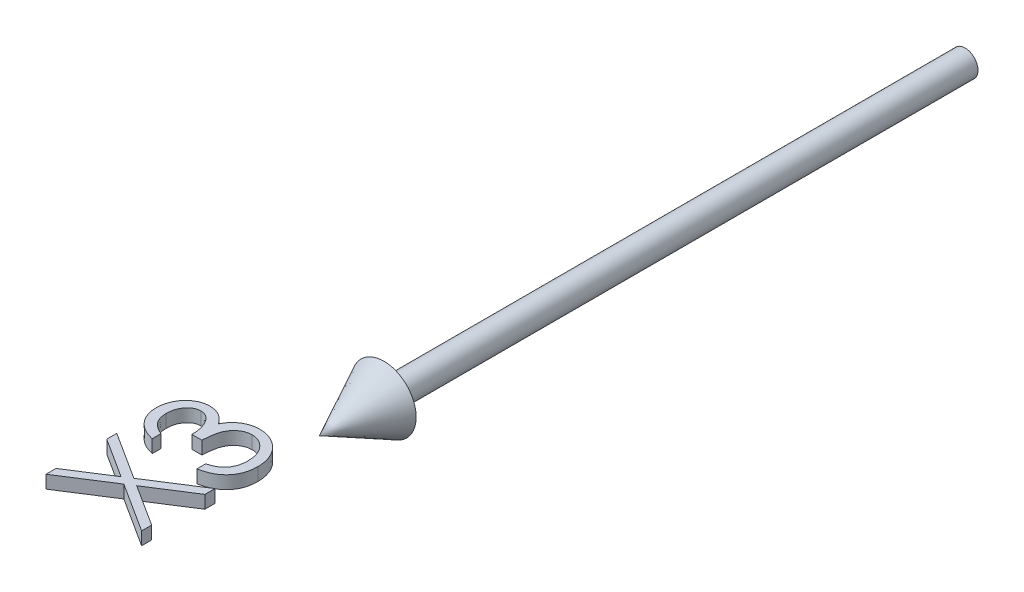
SolidWorks part; units mm, degrees
ref_plane "Front Plane" through (0, 0, 0) normal (0, 0, 1) x (1, 0, 0)
ref_plane "Top Plane" through (0, 0, 0) normal (0, 1, 0) x (1, 0, 0)
ref_plane "Right Plane" through (0, 0, 0) normal (1, 0, 0) x (0, 0, -1)
sketch "Sketch2" plane through (0, 0, 0) normal (0, 1, 0) x (1, 0, 0)
  line L0 (0, 41.95) -> (0, -114.4521) construction
  line L1 (-36.8894, 0) -> (41.4965, 0) construction
  line L2 (0, -100) -> (5, -90)
  line L3 (5, -90) -> (2, -90)
  line L4 (2, -90) -> (2, 0)
  line L5 (2, 0) -> (0, 0)
  line L6 (0, 0) -> (0, -100)
  dimension "D1" = 100
  dimension "D2" = 2
  dimension "D3" = 10
  dimension "D4" = 5
revolve "Revolve1" add sketch "Sketch2" angle 360 about L0
sketch "Sketch3" plane through (0, 0, 0) normal (0, 1, 0) x (1, 0, 0)
  line L0 (0, -103.9528) -> (0, -147.2622) construction
  line L1 (-18.6107, -118.3811) -> (18.3141, -118.3811) construction
  text T0 "X3" font "Century Gothic" height 15
extrude "Boss-Extrude1" add sketch "Sketch3" against normal blind 1 and the other way blind 1 separate body
equation "\"frame_arrow_length\"=100"
equation "\"D1@Sketch2\"=\"frame_arrow_length\""
equation "\"frame_arrow_odA\"=4"
equation "\"D2@Sketch2\"=\"frame_arrow_odA\"/2"
equation "\"frame_arrow_head_od\"=5"
equation "\"D4@Sketch2\"=\"frame_arrow_head_od\""
equation "\"frame_arrow_head_length\"=10"
equation "\"D3@Sketch2\"=\"frame_arrow_head_length\""
equation "\"tvarobot_theta1\"=30"
equation "\"link0_ringA_odA\"= 40"
equation "\"link0_ringA_odB\"= 25"
equation "\"link0_ringA_id\"= 20"
equation "\"link0_ringA_thickness\"= (\"link0_ringA_odB\" - \"link0_ringA_id\")/2"
equation "\"link0_ringA_height\"= 3"
equation "\"link0_ringA_heightA\"= 1.5"
equation "\"link0_ringA_heightB\"=\"link0_ringA_height\"-\"link0_ringA_heightA\""
equation "\"link0_ringB_odA\"= 40"
equation "\"link0_ringB_odB\"= 29"
equation "\"link0_ringB_id\"= \"link0_shaftA_bearing_id\"+1"
equation "\"link0_ringB_thickness\"= (\"link0_ringB_odB\" - \"link0_ringB_id\")/2"
equation "\"link0_ringB_height\"= 3"
equation "\"link0_ringB_heightA\"= 1.5"
equation "\"link0_ringB_heightB\"=\"link0_ringB_height\"-\"link0_ringB_heightA\""
equation "\"link0_shaftA_bearing_od\"=27"
equation "\"link0_shaftA_bearing_id\"=20"
equation "\"link0_shaftA_thrust_bearing_od\"=35"
equation "\"link0_shaftA_thrust_bearing_id\"=20.04"
equation "\"link0_shaftA_retaining_ring_id\"=18.5"
equation "\"link0_shaftA_retaining_ring_groove_width\"=1.5"
equation "\"link0_shaftA_spline_length\"=8.0"
equation "\"link0_shaftA_spline_depth\"=1.0"
equation "\"link0_shaftA_spline_width\"=4.0"
equation "\"link0_shaftA_odA\"=\"link0_shaftA_bearing_id\""
equation "\"link0_shaftA_odB\"=35"
equation "\"link0_shaftA_odC\"=\"link0_shaftA_bearing_id\""
equation "\"link0_shaftA_odD\"=\"link0_shaftA_odC\"-2*\"link0_shaftA_spline_depth\""
equation "\"link0_shaftA_odE\"=\"link0_shaftA_bearing_id\""
equation "\"link0_shaftA_odF\"=\"link0_shaftA_odE\"-2*\"link0_shaftA_spline_depth\""
equation "\"link0_shaftA_idA\"=10"
equation "\"link0_shaftA_idB\"=6"
equation "\"link0_shaftA_length\"=39.5"
equation "\"link0_shaftA_lengthA\"=8.0"
equation "\"link0_shaftA_lengthB\"=12.0"
equation "\"link0_shaftA_lengthC\"=35.0"
equation "\"link0_shaftA_lengthD\"=39.0"
equation "\"link0_shaftA_lengthE\"=\"link0_shaftA_length\"-\"link0_shaftA_lengthD\""
equation "\"link0_shaftA_offsetX\"=11"
equation "\"link0_shaftA_offsetY\"=0"
equation "\"link0_shaftA_bolt_pattern_dia\"=14"
equation "\"link0_motor_center_dist\"=26"
equation "\"link0_46t_pulley_spline_length\"=8"
equation "\"link0_46t_pulley_spline_depth\"=\"link0_shaftA_spline_depth\"*1.025"
equation "\"link0_46t_pulley_spline_width\"=\"link0_shaftA_spline_width\"*1.05"
equation "\"link0_46t_pulley_idA\"=\"link0_shaftA_bearing_id\"*1.025"
equation "\"link0_46t_pulley_idB\"=\"link0_46t_pulley_idA\"-2*\"link0_46t_pulley_spline_depth\""
equation "\"link0_shaftB_spline_length\"=10"
equation "\"link0_shaftB_spline_depth\"=1.0"
equation "\"link0_shaftB_spline_width\"=1.25"
equation "\"link0_shaftB_length\"=7"
equation "\"link0_shaftB_lengthA\"=1.5"
equation "\"link0_shaftB_lengthB\"=2.75"
equation "\"link0_shaftB_odA\"=32"
equation "\"link0_shaftB_odB\"=22"
equation "\"link0_shaftB_odC\"=20"
equation "\"link0_shaftB_idA\"=10"
equation "\"link0_shaftB_bolt_diameter\"=19"
equation "\"link0_shaftB_bearing_od\"=27"
equation "\"link0_shaftB_bearing_id\"=20"
equation "\"link0_motor_length\"=46.5"
equation "\"link0_motor_width\"=28.5"
equation "\"link0_motor_height\"=34"
equation "\"link0_motor_offset\"=8"
equation "\"link0_shellA_thickness\"=2.5"
equation "\"link0_shellB_thickness\"=\"link0_shellA_thickness\""
equation "\"link0_plateA_shellA_height\"=48"
equation "\"link0_shellA_width\" =\"link0_plateA_width\""
equation "\"link0_shellA_height\" = \"link0_plateA_shellA_height\"-\"link0_plateA_height\""
equation "\"link0_shellA_length\" = \"link0_plateA_lengthB\" "
equation "\"link0_shellB_length\"=\"link0_shellA_length\""
equation "\"link0_shellA_radius\" = 0.375*25.4"
equation "\"link0_shellA_radiusA\"= \"link0_plateA_radiusA\""
equation "\"link0_shellA_radiusB\"= \"link0_plateA_radiusB\""
equation "\"link0_shellA_radiusC\"= 3"
equation "\"link0_postA_height\"=7"
equation "\"link0_postA_width\"=16"
equation "\"link0_postA_length\"=20"
equation "\"link0_postA_posX\"=22"
equation "\"link0_postA_posY\"=17.5"
equation "\"link0_postA_pocket_width\"=6.0"
equation "\"link0_postA_pocket_length\"=2.5"
equation "\"link0_postA_pocket_depth\"=9"
equation "\"link0_postA_pocket_posZ\"=10"
equation "\"link0_postB_height\"=7"
equation "\"link0_postB_width\"=16"
equation "\"link0_postB_length\"=20"
equation "\"link0_postB_posX\"=22"
equation "\"link0_postB_posY\"=17.5"
equation "\"link0_postB_id\"=3.0"
equation "\"link0_postB_pocket_width\"=6.0"
equation "\"link0_postB_pocket_length\"=2.5"
equation "\"link0_postB_pocket_depth\"=9"
equation "\"link0_postB_pocket_posZ\"=10"
equation "\"link0_postC_height\"=7"
equation "\"link0_postC_width\"=16"
equation "\"link0_postC_length\"=20"
equation "\"link0_postC_posX\"=22"
equation "\"link0_postC_posY\"=17.5"
equation "\"link0_postC_id\"=3.0"
equation "\"link0_postC_pocket_width\"=6.0"
equation "\"link0_postC_pocket_length\"=2.5"
equation "\"link0_postC_pocket_depth\"=9"
equation "\"link0_postC_pocket_posZ\"=10"
equation "\"link0_postD_height\"=7"
equation "\"link0_postD_width\"=16"
equation "\"link0_postD_length\"=20"
equation "\"link0_postD_posX\"=22"
equation "\"link0_postD_posY\"=17.5"
equation "\"link0_postD_id\"=3.0"
equation "\"link0_postD_pocket_width\"=6.0"
equation "\"link0_postD_pocket_length\"=3.0"
equation "\"link0_postD_pocket_depth\"=9"
equation "\"link0_postD_pocket_posZ\"=10"
equation "\"link0_postE_height\"=5"
equation "\"link0_postE_width\"=16"
equation "\"link0_postE_length\"=\"link0_plateE_lengthA\"-\"link0_lip_height\""
equation "\"link0_postE_posZ\"=22"
equation "\"link0_postE_posX\"=17.5"
equation "\"link0_postE_posY\"=22"
equation "\"link0_postE_id\"=3.0"
equation "\"link0_postE_cbore_id\"=6.5"
equation "\"link0_postE_hole_id\"=3"
equation "\"link0_postF_posZ\"=22"
equation "\"link0_postF_posX\"=17.5"
equation "\"link0_postF_posY\"=\"link0_plateB_lengthA\"+4"
equation "\"link0_postF_id\"=3.0"
equation "\"link0_postF_cbore_id\"=6.5"
equation "\"link0_postF_hole_id\"=3"
equation "\"link0_postG_posZ\"=22"
equation "\"link0_postG_posX\"=17.5"
equation "\"link0_postG_posY\"=\"link0_plateB_lengthA\"+12"
equation "\"link0_postG_id\"=3.0"
equation "\"link0_postG_cbore_id\"=6.5"
equation "\"link0_postG_hole_id\"=3"
equation "\"link0_postHIJ_posY\"=6"
equation "\"link0_postH_posX\"=28"
equation "\"link0_postH_posY\"=20"
equation "\"link0_postH_posZ\"=20"
equation "\"link0_postH_length\"=10"
equation "\"link0_postI_posX\"=28"
equation "\"link0_postI_posY\"=20"
equation "\"link0_postI_posZ\"=135"
equation "\"link0_postI_length\"=10"
equation "\"link0_postJ_posX\"=28"
equation "\"link0_postJ_posY\"=20"
equation "\"link0_postJ_posZ\"=175"
equation "\"link0_postJ_length\"=10"
equation "\"link0_postK_posX\"=28"
equation "\"link0_postK_posY\"=20"
equation "\"link0_postK_posZ\"=175"
equation "\"link0_postK_length\"=10"
equation "\"link0_postL_posX\"=28"
equation "\"link0_postL_posY\"=20"
equation "\"link0_postL_posZ\"=135"
equation "\"link0_postL_length\"=10"
equation "\"link0_postM_posX\"=28"
equation "\"link0_postM_posY\"=20"
equation "\"link0_postM_posZ\"=35"
equation "\"link0_postM_length\"=10"
equation "\"link0_plateA_lengthA\"=30"
equation "\"link0_plateA_lengthB\"=150"
equation "\"link0_plateA_lengthC\"=30"
equation "\"link0_plateA_length\"=\"link0_plateA_lengthA\"+\"link0_plateA_lengthB\"+\"link0_plateA_lengthC\""
equation "\"link0_plateA_width\"=  68"
equation "\"link0_plateA_height\"= \"link0_plateA_radiusA\""
equation "\"link0_plateA_thickness\"=\"link0_shellA_thickness\""
equation "\"link0_plateA_radius\"= 9.5"
equation "\"link0_plateA_radiusA\"= 18"
equation "\"link0_plateA_radiusB\"= 18"
equation "\"link0_plateA_radiusC\"= 3"
equation "\"link0_plateB_length\"= 40"
equation "\"link0_plateB_width\"= \"link0_plateA_width\"*1.005"
equation "\"link0_plateB_height\"= \"link0_plateA_shellA_height\"*1.005"
equation "\"link0_plateB_lengthA\"=\"link0_lip_height\"+\"link0_plateD_thickness\"+\"link0_motor_mount_thickness\""
equation "\"link0_plateB_lengthB\"=\"link0_plateB_height\"-\"link0_plateB_lengthA\""
equation "\"link0_plateB_radiusA\"= \"link0_plateA_radiusA\""
equation "\"link0_plateB_radiusB\"= \"link0_plateA_radiusB\""
equation "\"link0_plateB_radiusC\"= 3"
equation "\"link0_plateB_idA\"=\"link0_shaftA_odC\"+1"
equation "\"link0_plateB_idB\"=\"link0_shaftA_bearing_od\"-2"
equation "\"link0_plateB_idC\"=\"link0_shaftA_bearing_od\"*1.005"
equation "\"link0_plateB_idD\"=\"link0_shaftA_thrust_bearing_od\"+1 "
equation "\"link0_plateB_depthA\"=1.0"
equation "\"link0_plateB_depthB\"=2.0"
equation "\"link0_plateB_depthC\"=8"
equation "\"link0_plateB_depthD\"=\"link0_plateB_length\"-\"link0_lip_height\"-\"link0_plateD_thickness\" "
equation "\"link0_plateC_length\"=\"link0_plateB_length\""
equation "\"link0_plateC_width\"= \"link0_plateB_width\""
equation "\"link0_plateC_height\"= .1*25.4"
equation "\"link0_plateA_hole_od\" = 0.1*25.4"
equation "\"link0_plateA_hole_delx\" = 0.5*25.4"
equation "\"link0_plateA_hole_delz\" = 0.75*25.4"
equation "\"link0_plateA_hole_offx\" = 0.0*25.4"
equation "\"link0_plateA_hole_offz\" = \"link0_plateA_length\"/2"
equation "\"link0_plateB_hole_od\" = 0.1*25.4"
equation "\"link0_plateB_hole_delx\"= 0.75*25.4"
equation "\"link0_plateB_hole_delz\"= 0.75*25.4"
equation "\"link0_plateB_hole_offx\"= 0.0*25.4"
equation "\"link0_plateB_hole_offz\"= 0.0*25.4"
equation "\"link0_plateC_hole_od\"= 0.1*25.4"
equation "\"link0_plateC_hole_delx\"= 0.75*25.4"
equation "\"link0_plateC_hole_delz\"= 0.75*25.4"
equation "\"link0_plateC_hole_offx\"= 0.0*25.4"
equation "\"link0_plateC_hole_offz\"= 0.0*25.4"
equation "\"link0_plateD_height\"=\"link0_plateB_height\"-2*\"link0_shellA_thickness\""
equation "\"link0_plateD_width\"=\"link0_plateB_width\"-2*\"link0_shellA_thickness\""
equation "\"link0_plateD_thickness\"=10"
equation "\"link0_plateD_radiusA\"=\"link0_plateB_radiusA\"-\"link0_shellA_thickness\""
equation "\"link0_plateD_odA\"= .375*25.4"
equation "\"link0_plateD_odB\"= .375*25.4"
equation "\"link0_plateD_bearing_id\"=20"
equation "\"link0_plateD_bearing_od\"=27"
equation "\"link0_plateE_radiusA\"=\"link0_plateA_radiusA\""
equation "\"link0_plateE_radiusB\"=\"link0_plateA_radiusB\""
equation "\"link0_plateE_radiusC\"=8.0"
equation "\"link0_plateE_length\"=30"
equation "\"link0_plateE_lengthA\"=16"
equation "\"link0_plateE_height\"=\"link0_plateB_height\""
equation "\"link0_plateE_width\"=\"link0_plateB_width\""
equation "\"link0_plateE_odA\"=\"gantry_coupler_id\"*0.99"
equation "\"link0_plateE_idA\"=\"link0_plateE_odA\"-20.0"
equation "\"link0_plateE_spline_depth\"=\"link0_poleA_spline_depth\"*1.05"
equation "\"link0_plateE_spline_width\"=\"link0_poleA_spline_width\"*1.075"
equation "\"link0_plateE_spline_length\"=\"link0_poleA_spline_length\""
equation "\"link0_plateE_coupler_length\"=46"
equation "\"link0_lip_height\"=5.0"
equation "\"link0_lip_thickness\"=2.0"
equation "\"link0_motor_mount_thickness\"=8.0"
equation "\"link0_motor_mount_idA\"=22"
equation "\"link0_motor_mount_idB\"=\"link0_shaftB_bearing_od\"*1.005"
equation "\"link0_motor_mount_idC\"=\"link0_shaftB_bearing_od\"-2"
equation "\"link0_motor_mount_depthA\"=5.5"
equation "\"link0_motor_mount_height\"=\"link0_plateD_height\""
equation "\"link0_motor_mount_width\"=\"link0_plateD_width\""
equation "\"link0_motor_mountL_height\"=36"
equation "\"link0_motor_mountL_heightA\"=12"
equation "\"link0_motor_mountL_length\"=50"
equation "\"link0_motor_mountL_lengthA\"=36"
equation "\"gantry_coupler_od\"=25.4*2.0"
equation "\"gantry_coupler_id\"=1.645*25.4"
equation "\"gantry_coupler_offsetX\"=\"link0_plateE_width\"/2"
equation "\"link0_poleA_odA\"=20"
equation "\"link0_poleA_odB\"=36"
equation "\"link0_poleA_idA\"=\"link0_poleA_odA\"-2*\"link0_poleA_thickness\""
equation "\"link0_poleA_idB\"=(\"link0_plateE_idA\"/2+1.5*\"link0_lip_thickness\")*1.04"
equation "\"link0_poleA_thickness\"=3.5"
equation "\"link0_poleA_length\"=100"
equation "\"link0_poleA_lengthA\"=18.5"
equation "\"link0_poleA_lengthB\"=80"
equation "\"link0_poleA_gasket_thickness\"=1.5"
equation "\"link0_poleA_spline_depth\"=1.0"
equation "\"link0_poleA_spline_width\"=4.0"
equation "\"link0_poleA_spline_length\"=10.0"
equation "\"link1_plateB_length\"=30"
equation "\"link1_lip_height\"=\"link0_lip_height\""
equation "\"link0_tension_plateA_width\"=12"
equation "\"link0_tension_plateA_lengthA\"=10.5"
equation "\"link0_tension_plateB_width\"=\"link0_tension_plateA_width\""
equation "\"link0_tension_plateB_lengthA\"=\"link0_tension_plateA_lengthA\""
equation "\"link0_tension_wheelA_posZ\"=7"
equation "\"link0_tension_wheelA_posX\"=\"link0_plateD_height\"/2-\"link0_tension_plateA_lengthA\""
equation "\"link0_m2_clear_hole_id\"=2.35"
equation "\"link0_m2_insert_hole_id\"=2.5"
equation "\"link0_m2_tap_hole_id\"=1.75"
equation "\"link0_m2_nut_socket_width\"=4.25"
equation "\"link0_m2_nut_socket_depth\"=2.5"
equation "\"link0_m2_cbore_id\"=3.75"
equation "\"link0_m2_cbore_depth\"=7"
equation "\"link0_m2_5_clear_hole_id\"=2.75"
equation "\"link0_m2_5_insert_hole_id\"=2.75"
equation "\"link0_m2_5_tap_hole_id\"=2.25"
equation "\"link0_m2_5_nut_socket_width\"=5.25"
equation "\"link0_m2_5_nut_socket_depth\"=2.5"
equation "\"link0_m2_5_cbore_id\"=4.75"
equation "\"link0_m2_5_cbore_depth\"=2.5"
equation "\"link0_m2_5_insert_access_length\"=6.0"
equation "\"link0_m2_5_insert_access_width\"=3.0"
equation "\"link0_m3_clear_hole_id\"=3.25"
equation "\"link0_m3_insert_hole_id\"=3"
equation "\"link0_m3_tap_hole_id\"=2.75"
equation "\"link0_m3_nut_socket_width\"=5.75"
equation "\"link0_m3_nut_socket_depth\"=4.0"
equation "\"link0_m3_cbore_id\"=5.75"
equation "\"link0_m3_cbore_depth\"=3.5"
equation "\"link0_m3_insert_access_length\"=4.5"
equation "\"link0_m3_insert_access_width\"=3.5"
equation "\"link0_rpi_mount_height\"=6"
equation "\"link0_rpi_mount_width\"=49"
equation "\"link0_rpi_mount_length\"=58"
equation "\"link0_rpi_mount_post_od\"=6"
equation "\"link0_rpi_mount_posZ\"=72"
equation "\"link0_rpi_mount_posX\"=11.5"
equation "\"link0_mcu_mount_height\"=5"
equation "\"link0_mcu_mount_width\"=49"
equation "\"link0_mcu_mount_length\"=58"
equation "\"link0_mcu_mount_post_od\"=6"
equation "\"link0_mcu_mount_posZ\"=164"
equation "\"link0_mcu_mount_posX\"=4"
equation "\"link0_pwr_mount_height\"=4"
equation "\"link0_pwr_mount_width\"=15.75"
equation "\"link0_pwr_mount_length\"=75.75"
equation "\"link0_pwr_mount_post_od\"=6"
equation "\"link0_pwr_mount_posZ\"=75"
equation "\"link0_pwr_mount_posX\"=16"
equation "\"link0_pwr_board_height\"=6"
equation "\"link0_pwr_board_width\"=21"
equation "\"link0_pwr_board_length\"=80"
